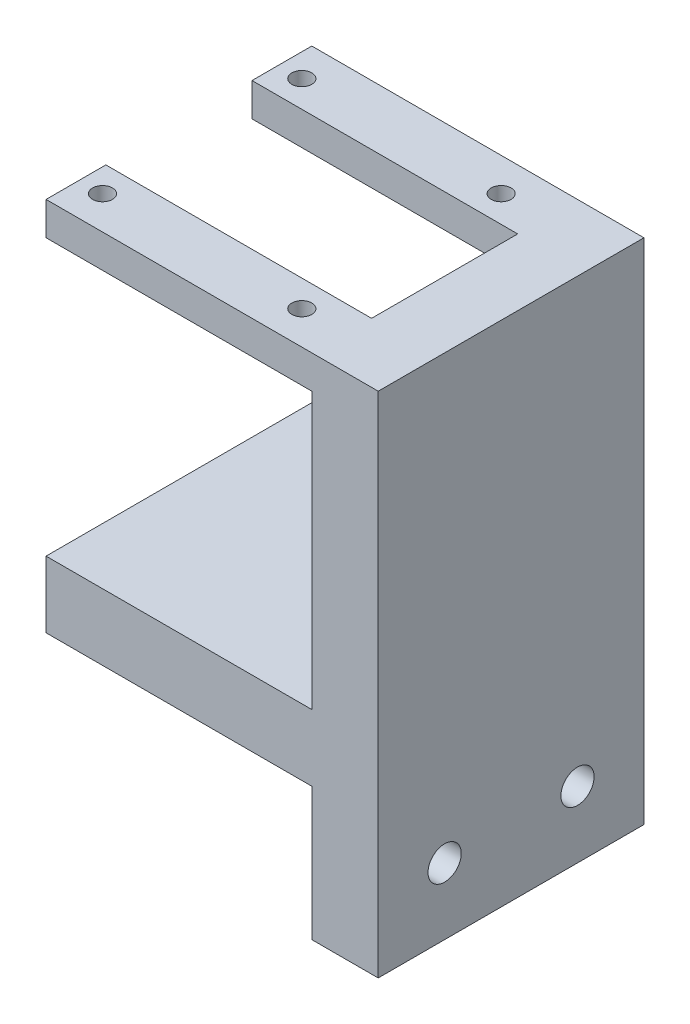
SolidWorks part; units mm, degrees
ref_plane "Front Plane" through (0, 0, 0) normal (0, 0, 1) x (1, 0, 0)
ref_plane "Top Plane" through (0, 0, 0) normal (0, 1, 0) x (1, 0, 0)
ref_plane "Right Plane" through (0, 0, 0) normal (1, 0, 0) x (0, 0, -1)
sketch "Sketch1" plane through (0, 0, 0) normal (1, 0, 0) x (0, 0, -1)
  line L0 (0, 55) -> (0, -55) construction
  line L5 (-20, 56.5) -> (20, 56.5)
  line L6 (-20, 56.5) -> (-20, 0)
  line L7 (-20, 0) -> (20, 0)
  line L8 (20, 56.5) -> (20, 0)
  line L9 (-20, 56.5) -> (20, 0) construction
  line L10 (-20, 0) -> (20, 56.5) construction
  line L11 (55, 0) -> (-55, 0) construction
  line L13 (-20, -20) -> (20, -20)
  line L14 (-20, -20) -> (-20, 0)
  line L15 (-20, 0) -> (20, 0)
  line L16 (20, -20) -> (20, 0)
  line L17 (-20, -20) -> (20, 0) construction
  line L18 (-20, 0) -> (20, -20) construction
  line L19 (10, -15) -> (-10, -15) construction
  line L20 (10, -15) -> (10, -5) construction
  line L21 (10, -5) -> (-10, -5) construction
  line L22 (-10, -15) -> (-10, -5) construction
  line L23 (10, -15) -> (-10, -5) construction
  line L24 (10, -5) -> (-10, -15) construction
  circle A0 centre (-10, -10) radius 2.5
  circle A1 centre (10, -10) radius 2.5
  point P1 (0, 28.25)
  point P10 (0, -10)
  point P11 (0, -10)
  dimension "D5" = 5
  dimension "D1" = 56.5
  dimension "D2" = 40
  dimension "D3" = 20
  dimension "D4" = 20
extrude "Boss-Extrude1" add sketch "Sketch1" along normal blind 10 contours L8 L5 L6 L7 | L13 L16 L7 L14 A1 A0 region at (0, 28.25, 0) region at (0, -10, 0)
sketch "Sketch3" plane through (0, 0, 0) normal (-1, 0, 0) x (0, 0, 1)
  line L0 (20, 56.5) -> (20, -20) construction
  line L1 (-20, 10) -> (20, 10)
  line L2 (-20, 10) -> (-20, 0)
  line L3 (-20, 0) -> (20, 0)
  line L4 (20, 10) -> (20, 0)
  line L5 (-20, 10) -> (20, 0) construction
  line L6 (-20, 0) -> (20, 10) construction
  dimension "D1" = 10
extrude "Boss-Extrude2" add sketch "Sketch3" along normal blind 40
sketch "Sketch4" plane through (0, 0, 0) normal (-1, 0, 0) x (0, 0, 1)
  line L13 (-20, 56.5) -> (-11, 56.5)
  line L14 (-20, 56.5) -> (-20, 51.5)
  line L15 (-20, 51.5) -> (-11, 51.5)
  line L16 (-11, 56.5) -> (-11, 51.5)
  dimension "D1" = 9
  dimension "D2" = 5
extrude "Boss-Extrude3" add sketch "Sketch4" along normal blind 40
sketch "Sketch5" plane through (0, 56.5, 0) normal (0, 1, 0) x (1, 0, 0)
  line L1 (-40, 20) -> (-36.5, 20) construction
  line L2 (-40, 20) -> (-40, 15) construction
  line L3 (-40, 15) -> (-36.5, 15) construction
  line L4 (-36.5, 20) -> (-36.5, 15) construction
  line L5 (10, 20) -> (-40, 20) construction
  line L7 (-1.5, 20) -> (-6.5, 20) construction
  line L8 (-1.5, 20) -> (-1.5, 15) construction
  line L9 (-1.5, 15) -> (-6.5, 15) construction
  line L10 (-6.5, 20) -> (-6.5, 15) construction
  circle A0 centre (-36.5, 15) radius 1.5
  circle A1 centre (-6.5, 15) radius 1.5
  dimension "D3" = 3
  dimension "D7" = 3
  dimension "D1" = 3.5
  dimension "D2" = 5
  dimension "D4" = 5
  dimension "D5" = 5
  dimension "D6" = 30
extrude "Cut-Extrude1" cut sketch "Sketch5" against normal up to next
mirror "Mirror2" about plane through (0, 0, 0) normal (0, 0, 1) of "Cut-Extrude1", "Boss-Extrude3"
